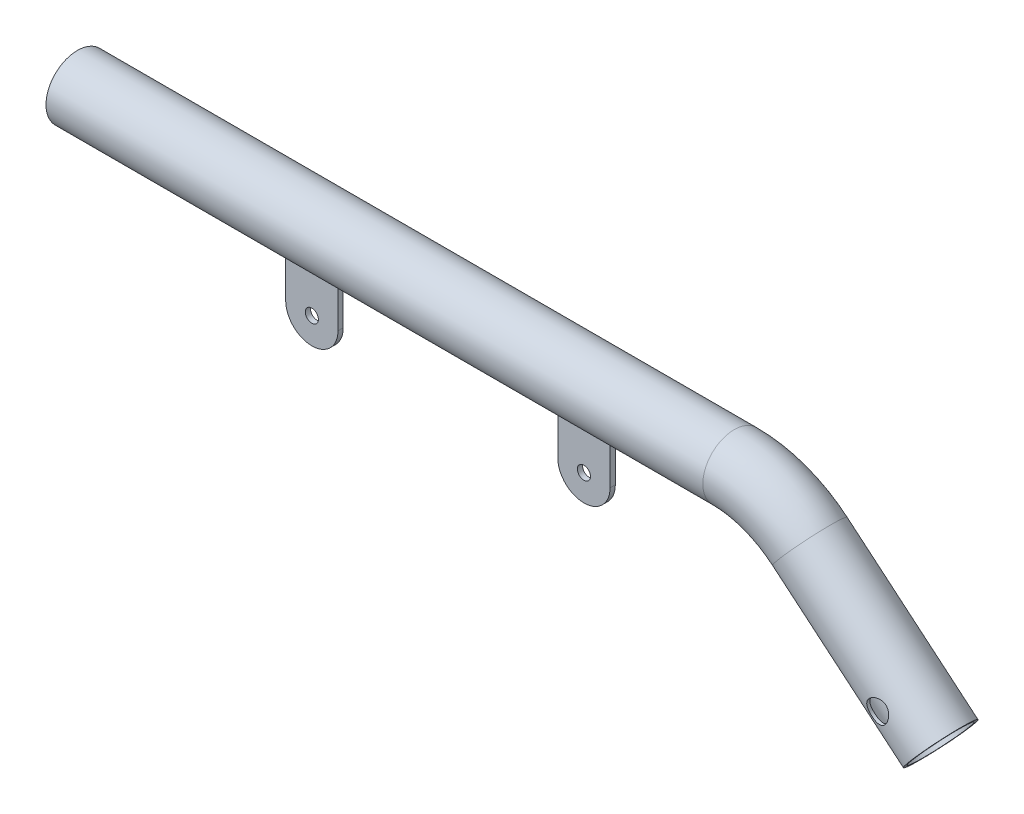
SolidWorks part; units mm, degrees
ref_plane "Front Plane" through (0, 0, 0) normal (0, 0, 1) x (1, 0, 0)
ref_plane "Top Plane" through (0, 0, 0) normal (0, 1, 0) x (1, 0, 0)
ref_plane "Right Plane" through (0, 0, 0) normal (1, 0, 0) x (0, 0, -1)
sketch "Sketch1" plane through (0, 0, 0) normal (0, 0, 1) x (1, 0, 0)
  line L0 (-209.3679, 0) -> (41.7067, 0)
  line L1 (70.6321, -10.528) -> (120.6321, -52.483)
  arc A0 (70.6321, -10.528) -> (41.7067, 0) centre (41.7067, -45) ccw
  dimension "D2" = 45
  dimension "D1" = 140
  dimension "D3" = 330
  dimension "D4" = 50
ref_plane "Plane1" through (-209.3679, 0, 0) normal (1, 0, 0) x (0, 0, -1)
sketch "Sketch2" plane through (-209.3679, 0, 0) normal (1, 0, 0) x (0, 0, -1)
  circle A0 centre (0, 0) radius 12
  circle A1 centre (0, 0) radius 10.8
  dimension "D1" = 1.2
sweep "Sweep1" add profiles "Sketch2" path "Sketch1"
sketch "Sketch3" plane through (0, 0, 0) normal (0, 0, 1) x (1, 0, 0)
  line L0 (120.6321, -52.483) -> (70.6321, -10.528) construction
  line L1 (112.9187, -61.6755) -> (128.3456, -43.2904) construction
  line L2 (78.3456, -1.3355) -> (62.9187, -19.7205) construction
  line L3 (-209.3679, 0) -> (41.7067, 0) construction
  line L4 (-209.3679, 12) -> (-209.3679, -12) construction
  line L5 (41.7067, 12) -> (41.7067, -12) construction
  circle A0 centre (108.2587, -42.1004) radius 4.1426
extrude "Cut-Extrude1" cut sketch "Sketch3" against normal blind 20 and the other way blind 20
sketch "Sketch4" plane through (0, 0, 0) normal (0, 0, 1) x (1, 0, 0)
  line L3 (-128.7413, 0) -> (-128.7413, -30)
  line L8 (-24.7413, 0) -> (-4.7413, 0)
  line L9 (-24.7413, 0) -> (-24.7413, -30)
  line L11 (-4.7413, 0) -> (-4.7413, -30)
  line L12 (-128.7413, 0) -> (-108.7413, 0)
  line L13 (-108.7413, 0) -> (-108.7413, -30)
  line L14 (-14.7413, 0) -> (-118.7413, 0) construction
  circle A0 centre (108.2587, -42.1004) radius 4.1426
  arc A1 (-24.7413, -30) -> (-4.7413, -30) centre (-14.7413, -30) ccw
  circle A2 centre (-14.7413, -30) radius 2.5
  arc A3 (-128.7413, -30) -> (-108.7413, -30) centre (-118.7413, -30) ccw
  circle A4 centre (-118.7413, -30) radius 2.5
  point P21 (-14.7413, 0)
  dimension "D3" = 123
  dimension "D1" = 20
  dimension "D2" = 30
  dimension "D4" = 104
  dimension "D5" = 30
extrude "Boss-Extrude1" add sketch "Sketch4" along normal blind 1 and the other way blind 1 contours L3 A3 L13 L12 | A1 L11 L8 L9 | A4 | A2
sketch "Sketch5" plane through (-209.3679, 0, 0) normal (-1, 0, 0) x (0, 0, 1)
  circle A0 centre (0, 0) radius 10.8
extrude "Cut-Extrude2" cut sketch "Sketch5" against normal blind 240
